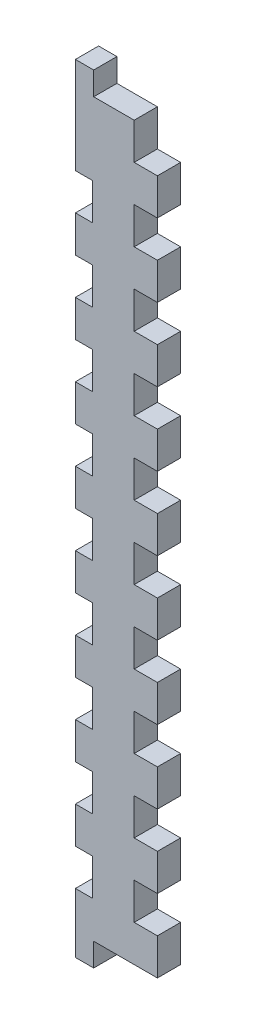
SolidWorks part; units mm, degrees
ref_plane "Front Plane" through (0, 0, 0) normal (0, 0, 1) x (1, 0, 0)
ref_plane "Top Plane" through (0, 0, 0) normal (0, 1, 0) x (1, 0, 0)
ref_plane "Right Plane" through (0, 0, 0) normal (1, 0, 0) x (0, 0, -1)
sketch "Sketch1" plane through (0, 0, 0) normal (0, 0, 1) x (1, 0, 0)
  line L1 (-11.2141, -100) -> (11.2141, -100)
  line L2 (-11.2141, -100) -> (-11.2141, 100)
  line L3 (-11.2141, 100) -> (11.2141, 100)
  line L4 (11.2141, -100) -> (11.2141, 100)
  line L5 (-11.2141, -100) -> (11.2141, 100) construction
  line L6 (-11.2141, 100) -> (11.2141, -100) construction
  point P0 (0, 0)
  dimension "D1" = 22.4282
  dimension "D2" = 200
extrude "Boss-Extrude1" add sketch "Sketch1" along normal blind 6.35
sketch "Sketch2" plane through (0, 0, 6.35) normal (0, 0, 1) x (1, 0, 0)
  line L1 (-6.5913, -80) -> (-11.2141, -80)
  line L2 (-6.5913, -80) -> (-6.5913, -90)
  line L3 (-6.5913, -90) -> (-11.2141, -90)
  line L4 (-11.2141, -80) -> (-11.2141, -90)
  line L6 (-11.2141, 100) -> (-11.2141, -100) construction
  line L13 (-11.2141, -100) -> (11.2141, -100) construction
  point P8 (-6.5913, -85)
  dimension "D2" = 4.6228
  dimension "D3" = 10
  dimension "D1" = 10
extrude "Cut-Extrude2" cut sketch "Sketch2" against normal blind 6.35
sketch "Sketch13" plane through (0, 0, 6.35) normal (0, 0, 1) x (1, 0, 0)
  line L0 (11.2141, -100) -> (11.2141, 100) construction
  line L1 (4.8641, -90) -> (11.2141, -90)
  line L2 (4.8641, -90) -> (4.8641, -80)
  line L3 (4.8641, -80) -> (11.2141, -80)
  line L4 (11.2141, -90) -> (11.2141, -80)
  line L5 (-6.5913, -80) -> (-11.2141, -80) construction
  line L7 (-11.2141, -90) -> (-6.5913, -90) construction
  dimension "D1" = 6.35
extrude "Cut-Extrude4" cut sketch "Sketch13" against normal blind 6.35
pattern_linear "LPattern1" count 9 spacing 20 along (0, 1, 0) of "Cut-Extrude2"
pattern_linear "LPattern2" count 10 spacing 20 along (0, 1, 0) of "Cut-Extrude4"
sketch "Sketch14" plane through (0, 0, 0) normal (0, 0, 1) x (1, 0, 0)
  line L0 (-11.2141, -100) -> (11.2141, -100) construction
  line L1 (-11.2141, 100) -> (-6.2103, 100)
  line L2 (-11.2141, 100) -> (-11.2141, 106.35)
  line L3 (-11.2141, 106.35) -> (-6.2103, 106.35)
  line L4 (-6.2103, 100) -> (-6.2103, 106.35)
  line L5 (-11.2141, -100) -> (-6.2103, -100)
  line L6 (-11.2141, -100) -> (-11.2141, -106.35)
  line L7 (-11.2141, -106.35) -> (-6.2103, -106.35)
  line L8 (-6.2103, -100) -> (-6.2103, -106.35)
  line L9 (4.8641, 100) -> (-11.2141, 100) construction
  dimension "D1" = 6.35
  dimension "D2" = 6.35
  dimension "D3" = 5.0038
  dimension "D4" = 5.0038
extrude "Boss-Extrude4" add sketch "Sketch14" along normal blind 6.35
equation "\"z\"= 20cm"
equation "\"D2@Sketch1\"=\"z\""
equation "\"tWidth\"= 1cm"
equation "\"tHeight02\"= 0.182in"
equation "\"D3@Sketch2\"=\"tWidth\""
equation "\"tHeight01\"= .25in"
equation "\"D2@Sketch2\"=\"tHeight02\""
equation "\"D1@Cut-Extrude2\"=\"tHeight01\""
equation "\"D1@Sketch13\"=\"tHeight01\""
equation "\"D1@Cut-Extrude4\"=\"tHeight01\""
equation "\"D1@Sketch2\"=\"tWidth\""
equation "\"D1@Boss-Extrude4\"=\"tHeight01\""
equation "\"D2@Sketch14\"=\"tHeight01\""
equation "\"D1@Sketch14\"=\"tHeight01\""
